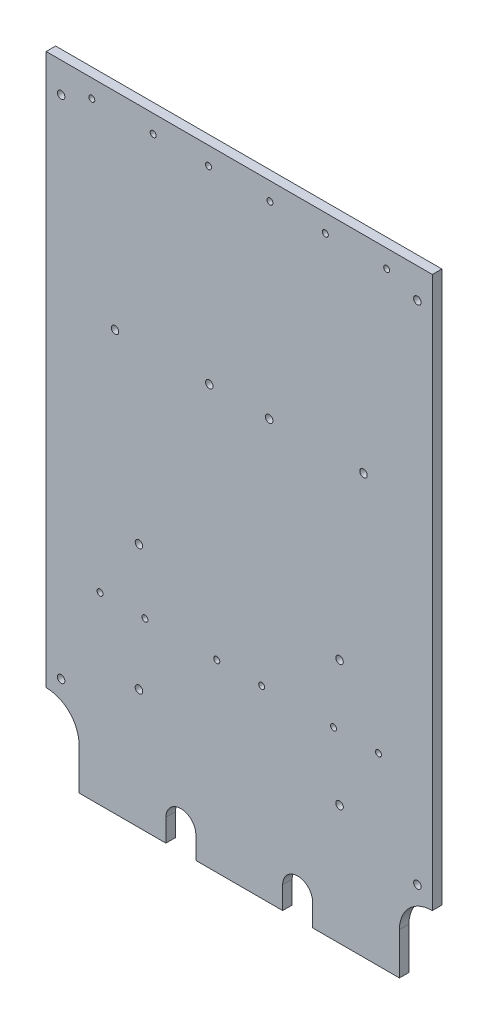
SolidWorks part; units mm, degrees
ref_plane "Front Plane" through (0, 0, 0) normal (0, 0, 1) x (1, 0, 0)
ref_plane "Top Plane" through (0, 0, 0) normal (0, 1, 0) x (1, 0, 0)
ref_plane "Right Plane" through (0, 0, 0) normal (1, 0, 0) x (0, 0, -1)
sketch "Sketch1" plane through (0, 0, 0) normal (0, 0, 1) x (1, 0, 0)
  line L0 (-64.5, 104.5) -> (64.5, -104.5) construction
  line L1 (-64.5, 104.5) -> (64.5, 104.5)
  line L2 (-64.5, 104.5) -> (-64.5, -104.5)
  line L3 (-64.5, -104.5) -> (64.5, -104.5)
  line L4 (64.5, 104.5) -> (64.5, -104.5)
  dimension "D1" = 129
  dimension "D2" = 209
extrude "Boss-Extrude1" add sketch "Sketch1" along normal blind 3.175
sketch "Sketch2" plane through (0, 0, 3.175) normal (0, 0, 1) x (1, 0, 0)
  line L0 (0, 104.5) -> (0, -104.5) construction
  line L1 (64.5, 104.5) -> (-64.5, 104.5) construction
  line L2 (-64.5, -104.5) -> (64.5, -104.5) construction
  line L3 (-59.5, 104.5) -> (-59.5, -104.5) construction
  line L4 (-64.5, 104.5) -> (-64.5, -104.5) construction
  line L5 (-64.5, -104.5) -> (-53.5, -104.5)
  line L6 (-64.5, -104.5) -> (-64.5, -79.5)
  line L7 (-64.5, -79.5) -> (-53.5, -79.5)
  line L8 (-53.5, -104.5) -> (-53.5, -79.5)
  line L9 (53.5, -104.5) -> (53.5, -79.5)
  line L10 (64.5, -104.5) -> (53.5, -104.5)
  line L11 (64.5, -104.5) -> (64.5, -79.5)
  line L12 (64.5, -79.5) -> (53.5, -79.5)
  circle A0 centre (-59.5, 94.5) radius 1.25
  circle A1 centre (-59.5, -74.5) radius 1.25
  circle A2 centre (59.5, -74.5) radius 1.25
  circle A3 centre (59.5, 94.5) radius 1.25
  dimension "D3" = 2.5
  dimension "D5" = 199
  dimension "D6" = 30
  dimension "D1" = 11
  dimension "D2" = 25
  dimension "D4" = 5
extrude "Cut-Extrude1" cut sketch "Sketch2" against normal through all
fillet "Fillet1" radius 11 2 edges at (53.5, -79.5, 1.5875) (-53.5, -79.5, 1.5875)
sketch "Sketch3" plane through (0, 0, 3.175) normal (0, 0, 1) x (1, 0, 0)
  line L0 (0, 104.5) -> (0, -104.5) construction
  line L1 (64.5, 104.5) -> (-64.5, 104.5) construction
  line L2 (-53.5, -104.5) -> (53.5, -104.5) construction
  line L3 (-10.25, 98.5) -> (10.25, 98.5) construction
  line L4 (7.5, -43) -> (-7.5, -43) construction
  circle A0 centre (-10.25, 98.5) radius 1
  circle A1 centre (10.25, 98.5) radius 1
  circle A2 centre (-7.5, -43) radius 1
  circle A3 centre (7.5, -43) radius 1
  point P10 (0, -43)
  point P11 (0, 98.5)
  dimension "D5" = 2
  dimension "D1" = 20.5
  dimension "D2" = 6
  dimension "D3" = 141.5
  dimension "D4" = 15
extrude "Cut-Extrude2" cut sketch "Sketch3" against normal through all
pattern_linear "LPattern1" count 2 spacing 39 along (1, 0, 0) count 2 spacing 39 along (-1, 0, 0) of "Cut-Extrude2"
sketch "Sketch4" plane through (0, 0, 3.175) normal (0, 0, 1) x (1, 0, 0)
  line L0 (-19.5, -104.5) -> (-19.5, -97) construction
  line L1 (-53.5, -104.5) -> (53.5, -104.5) construction
  line L2 (-24.5, -104.5) -> (-24.5, -97)
  line L3 (-14.5, -104.5) -> (-14.5, -97)
  line L4 (19.5, -104.5) -> (19.5, -97) construction
  line L5 (14.5, -104.5) -> (14.5, -97)
  line L6 (24.5, -104.5) -> (24.5, -97)
  line L7 (-31.5, -43) -> (-7.5, -43) construction
  line L8 (7.5, -43) -> (31.5, -43) construction
  line L9 (19.5, -43) -> (19.5, -97) construction
  line L10 (-19.5, -43) -> (-19.5, -97) construction
  arc A0 (-24.5, -104.5) -> (-14.5, -104.5) centre (-19.5, -104.5) ccw
  arc A1 (-14.5, -97) -> (-24.5, -97) centre (-19.5, -97) ccw
  arc A2 (14.5, -104.5) -> (24.5, -104.5) centre (19.5, -104.5) ccw
  arc A3 (24.5, -97) -> (14.5, -97) centre (19.5, -97) ccw
  point P4 (-19.5, -100.75)
  point P9 (19.5, -100.75)
  dimension "D2" = 5
  dimension "D1" = 7.5
extrude "Cut-Extrude3" cut sketch "Sketch4" against normal through all
sketch "Sketch5" plane through (0, 0, 3.175) normal (0, 0, 1) x (1, 0, 0)
  line L0 (-41.5, 35.5) -> (-10, 35.5) construction
  line L1 (-10, 35.5) -> (10, 35.5) construction
  line L2 (10, 35.5) -> (41.5, 35.5) construction
  line L3 (0, 35.5) -> (0, 0) construction
  line L4 (24.5, -104.5) -> (53.5, -104.5) construction
  circle A0 centre (-10, 35.5) radius 1.25
  circle A1 centre (-41.5, 35.5) radius 1.25
  circle A2 centre (10, 35.5) radius 1.25
  circle A3 centre (41.5, 35.5) radius 1.25
  dimension "D2" = 2.5
  dimension "D1" = 31.5
  dimension "D3" = 140
  dimension "D4" = 20
extrude "Cut-Extrude4" cut sketch "Sketch5" against normal through all
sketch "Sketch6" plane through (0, 0, 0) normal (0, 0, -1) x (-1, 0, 0)
  line L0 (0, 0) -> (0, -22.5) construction
  line L1 (-33.5, -22.5) -> (33.5, -22.5) construction
  line L2 (-33.5, -22.5) -> (-33.5, -64.5) construction
  line L3 (-33.5, -64.5) -> (33.5, -64.5) construction
  line L4 (33.5, -22.5) -> (33.5, -64.5) construction
  circle A0 centre (-33.5, -22.5) radius 1.25
  circle A1 centre (33.5, -22.5) radius 1.25
  circle A2 centre (33.5, -64.5) radius 1.25
  circle A3 centre (-33.5, -64.5) radius 1.25
  dimension "D4" = 2.5
  dimension "D1" = 67
  dimension "D2" = 42
  dimension "D3" = 22.5
extrude "Cut-Extrude5" cut sketch "Sketch6" against normal through all
